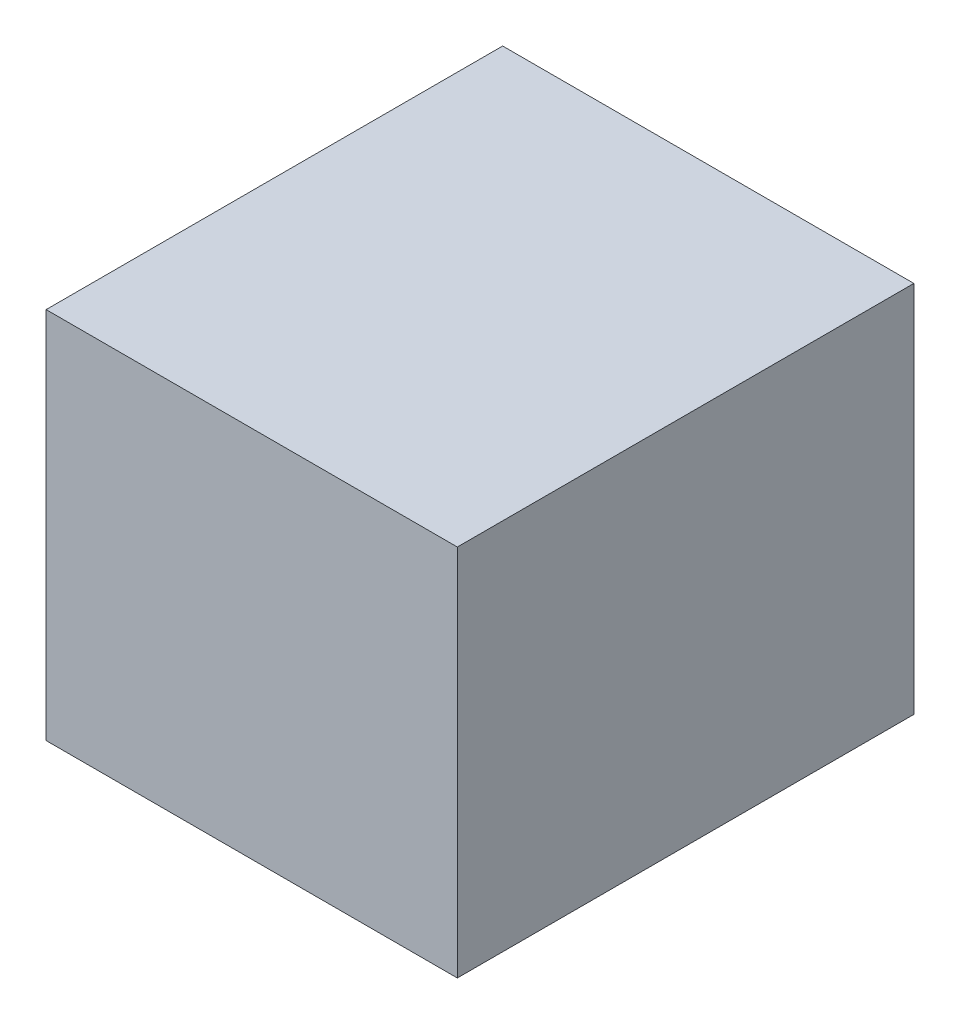
SolidWorks part; units mm, degrees
ref_plane "Ön Düzlem" through (0, 0, 0) normal (0, 0, 1) x (1, 0, 0)
ref_plane "Üst Düzlem" through (0, 0, 0) normal (0, 1, 0) x (1, 0, 0)
ref_plane "Sağ Düzlem" through (0, 0, 0) normal (1, 0, 0) x (0, 0, -1)
sketch "Çizim1" plane through (0, 0, 0) normal (0, 0, 1) x (1, 0, 0)
  line L1 (-49.53, 44.958) -> (49.53, 44.958)
  line L2 (-49.53, 44.958) -> (-49.53, -44.958)
  line L3 (-49.53, -44.958) -> (49.53, -44.958)
  line L4 (49.53, 44.958) -> (49.53, -44.958)
  line L5 (-49.53, 44.958) -> (49.53, -44.958) construction
  line L6 (-49.53, -44.958) -> (49.53, 44.958) construction
  point P0 (0, 0)
  dimension "D1" = 99.06
  dimension "D2" = 89.916
extrude "Yükseklik-Ekstrüzyon1" add sketch "Çizim1" along normal blind 54.991 and the other way blind 54.991
